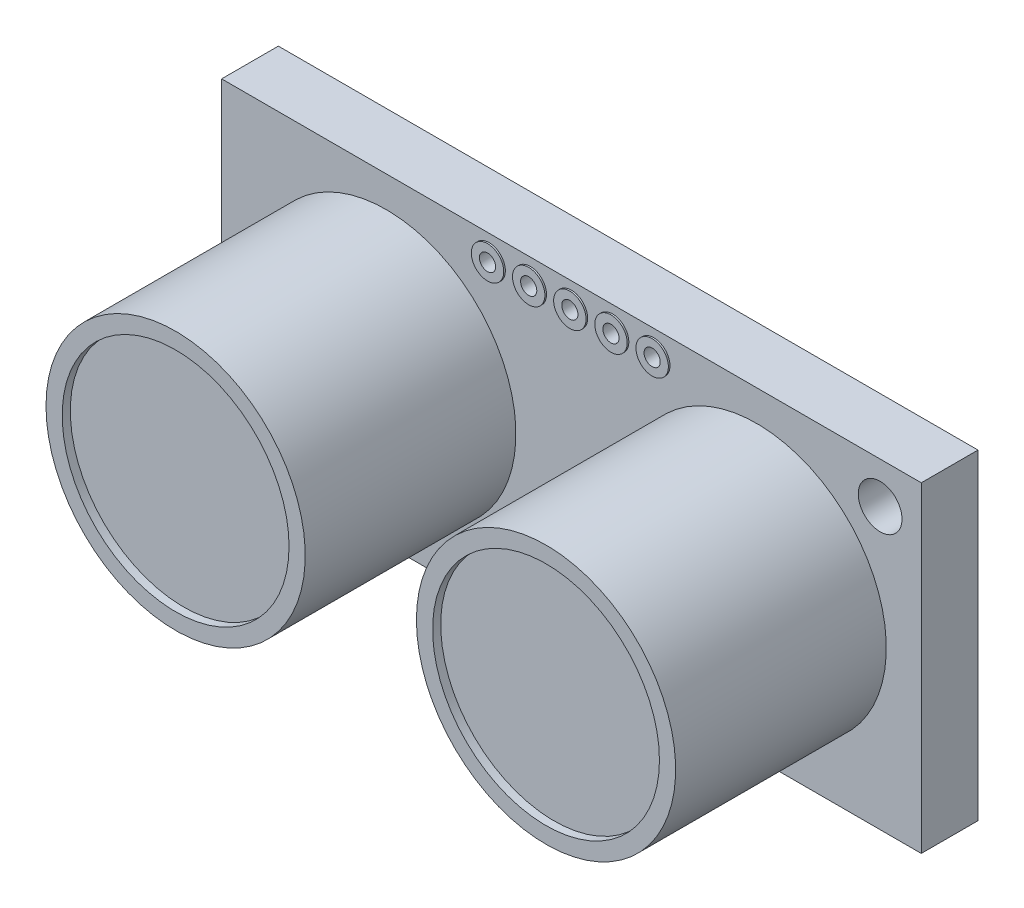
SolidWorks part; units mm, degrees
ref_plane "Front Plane" through (0, 0, 0) normal (0, 0, 1) x (1, 0, 0)
ref_plane "Top Plane" through (0, 0, 0) normal (0, 1, 0) x (1, 0, 0)
ref_plane "Right Plane" through (0, 0, 0) normal (1, 0, 0) x (0, 0, -1)
sketch "Sketch1" plane through (0, 0, 0) normal (0, 0, 1) x (1, 0, 0)
  line L0 (-21.59, 9.906) -> (21.59, 9.906)
  line L1 (-21.59, 9.906) -> (-21.59, -9.906)
  line L2 (-21.59, -9.906) -> (21.59, -9.906)
  line L3 (21.59, 9.906) -> (21.59, -9.906)
  line L4 (0, 9.906) -> (0, -9.906) construction
  line L5 (-21.59, 0) -> (21.59, 0) construction
  circle A2 centre (-19.05, -7.366) radius 1.35
  circle A3 centre (19.05, 7.366) radius 1.35
  point P16 (0, 0)
  point P26 (-21.59, 0)
  point P30 (21.59, 0)
  dimension "D16" = 2.7
  dimension "D4" = 2.54
  dimension "D2" = 2.54
  dimension "D3" = 2.54
  dimension "D5" = 2.54
  dimension "D12" = 43.18
  dimension "D13" = 19.812
other "AlignGroup1"
other "AlignGroup2"
other "AlignGroup3"
other "AlignGroup4"
other "AlignGroup5"
other "AlignGroup6"
extrude "Boss-Extrude1" add sketch "Sketch1" along normal blind 3.5
sketch "Sketch2" plane through (0, 0, 3.5) normal (0, 0, 1) x (1, 0, 0)
  line L1 (-21.59, -9.906) -> (21.59, -9.906) construction
  line L2 (0, -9.906) -> (0, 9.906) construction
  line L3 (21.59, 9.906) -> (-21.59, 9.906) construction
  circle A0 centre (-11.43, 0) radius 8
  circle A1 centre (11.43, 0) radius 8
  dimension "D1" = 7.62
  dimension "D3" = 16
  dimension "D2" = 7.366
extrude "Boss-Extrude2" add sketch "Sketch2" along normal blind 13
sketch "Sketch3" plane through (0, 0, 16.5) normal (0, 0, 1) x (1, 0, 0)
  circle A2 centre (-11.43, 0) radius 7
  circle A3 centre (-11.43, 0) radius 7
  circle A5 centre (11.43, 0) radius 7
  circle A6 centre (11.43, 0) radius 7
  dimension "D1" = 1
  dimension "D2" = 1
extrude "Cut-Extrude1" cut sketch "Sketch3" against normal blind 0.5
sketch "Sketch4" plane through (0, 0, 3.5) normal (0, 0, 1) x (1, 0, 0)
  line L0 (0, 9.906) -> (0, -9.906) construction
  line L1 (21.59, 9.906) -> (-21.59, 9.906) construction
  line L2 (-21.59, -9.906) -> (21.59, -9.906) construction
  line L3 (-21.59, 0) -> (21.59, 0) construction
  line L4 (-21.59, 9.906) -> (-21.59, -9.906) construction
  line L5 (21.59, -9.906) -> (21.59, 9.906) construction
  circle A0 centre (0, 8.406) radius 0.5
  circle A1 centre (2.54, 8.406) radius 0.5
  circle A2 centre (5.08, 8.406) radius 0.5
  circle A3 centre (-5.08, 8.406) radius 0.5
  circle A4 centre (-2.54, 8.406) radius 0.5
  circle A5 centre (-5.08, -8.406) radius 0.5
  circle A6 centre (-2.54, -8.406) radius 0.5
  circle A7 centre (0, -8.406) radius 0.5
  circle A8 centre (2.54, -8.406) radius 0.5
  circle A9 centre (5.08, -8.406) radius 0.5
  dimension "D1" = 1
  dimension "D3" = 2.54
  dimension "D2" = 2.54
  dimension "D4" = 1.5
extrude "Extrude-Thin4" add sketch "Sketch4" along normal blind 0.1 and the other way blind 3.6 thin contours A5 | A6 | A7 | A8 | A9 | A2 | A1 | A0 | A4 | A3 thin type one direction wall 0.5
sketch "Sketch11" plane through (0, 0, 3.5) normal (0, 0, 1) x (1, 0, 0)
  circle A0 centre (-5.08, -8.406) radius 0.5
  circle A1 centre (-2.54, -8.406) radius 0.5
  circle A2 centre (0, -8.406) radius 0.5
  circle A3 centre (2.54, -8.406) radius 0.5
  circle A4 centre (5.08, -8.406) radius 0.5
  circle A5 centre (-5.08, 8.406) radius 0.5
  circle A6 centre (-2.54, 8.406) radius 0.5
  circle A7 centre (0, 8.406) radius 0.5
  circle A8 centre (2.54, 8.406) radius 0.5
  circle A9 centre (5.08, 8.406) radius 0.5
extrude "Cut-Extrude2" cut sketch "Sketch11" against normal through all
sketch "Sketch12" plane through (0, 0, 0) normal (0, 0, -1) x (-1, 0, 0)
  line L1 (20.0845, -7.493) -> (20.0845, 7.493) construction
  text T0 "SRF05" font "Arial Rounded MT Bold" height in points 8
extrude "Boss-Extrude3" add sketch "Sketch12" along normal blind 0.001
